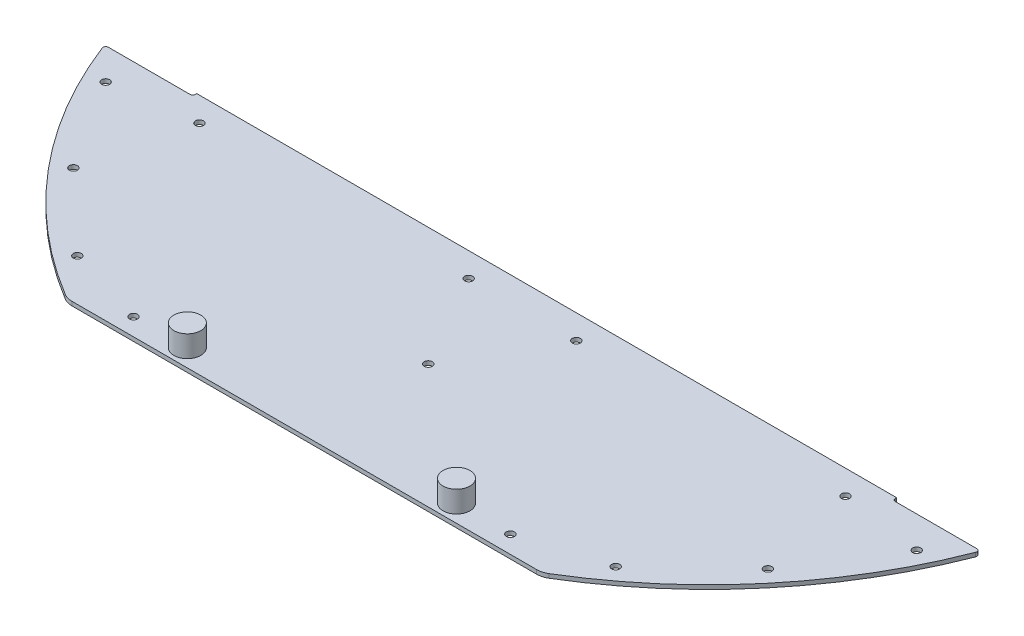
SolidWorks part; units mm, degrees
material "3.3535 (EN-AW 5754)"
ref_plane "Plan de face" through (0, 0, 0) normal (0, 0, 1) x (1, 0, 0)
ref_plane "Plan de dessus" through (0, 0, 0) normal (0, 1, 0) x (1, 0, 0)
ref_plane "Plan de droite" through (0, 0, 0) normal (1, 0, 0) x (0, 0, -1)
sketch "Esquisse1" plane through (0, 0, 0) normal (0, 1, 0) x (1, 0, 0)
  line L0 (0, 0) -> (0, -150) construction
  line L1 (-130, -60) -> (130, -60)
  line L2 (130, -60) -> (130, -61.5)
  line L3 (-88.1816, -150) -> (88.1816, -150)
  line L6 (162.769, -61.5) -> (130, -61.5)
  line L8 (-162.769, -61.5) -> (-130, -61.5)
  line L9 (-130, -60) -> (-130, -61.5)
  circle A0 centre (-120, -69) radius 1.5
  circle A1 centre (-20, -69) radius 1.5
  circle A2 centre (20, -69) radius 1.5
  circle A3 centre (120, -69) radius 1.5
  circle A4 centre (0, -104) radius 1.5
  arc A10 (-162.769, -61.5) -> (-88.1816, -150) centre (0, 0) ccw
  arc A11 (88.1816, -150) -> (162.769, -61.5) centre (0, 0) ccw
  dimension "D2" = 60
  dimension "D3" = 9
  dimension "D4" = 3
  dimension "D5" = 240
  dimension "D7" = 40
  dimension "D8" = 44
  dimension "D10" = 260
  dimension "D12" = 1.5
  dimension "D13" = 348
  dimension "D6" = 150
extrude "Boss.-Extru.1" add sketch "Esquisse1" along normal blind 1.5
fillet "Congé1" radius 7 2 edges at (88.1816, 0.75, 150) (-88.1816, 0.75, 150)
fillet "Congé2" radius 1 4 edges at (-130, 0.75, 61.5) (130, 0.75, 61.5) (162.769, 0.75, 61.5) (-162.769, 0.75, 61.5)
sketch "Esquisse2" plane through (0, 1.5, 0) normal (0, 1, 0) x (1, 0, 0)
  line L0 (-150.6593, -73.1985) -> (-129.0082, -106.8322) construction
  line L1 (-129.0082, -106.8322) -> (-100, -134.3735) construction
  line L2 (0, 0) -> (0, -150) construction
  line L3 (-86.2554, -150) -> (86.2554, -150) construction
  circle A0 centre (-150.6593, -73.1985) radius 1.5
  circle A1 centre (-129.0082, -106.8322) radius 1.5
  circle A2 centre (-100, -134.3735) radius 1.5
  circle A3 centre (-70, -143.5) radius 1.5
  circle A4 centre (-50, -143.5) radius 1.5
  circle A5 centre (0, 0) radius 167.5 construction
  circle A6 centre (150.6593, -73.1985) radius 1.5
  circle A7 centre (129.0082, -106.8322) radius 1.5
  circle A8 centre (100, -134.3735) radius 1.5
  circle A9 centre (70, -143.5) radius 1.5
  circle A10 centre (50, -143.5) radius 1.5
  arc A11 (-162.2481, -62.8613) -> (-89.8709, -148.994) centre (0, 0) ccw construction
  dimension "D1" = 40
  dimension "D2" = 3
  dimension "D4" = 6.5
  dimension "D5" = 140
  dimension "D6" = 100
  dimension "D7" = 6.5
  dimension "D3" = 100
extrude "Enlèv. mat.-Extru.1" cut sketch "Esquisse2" against normal through all
sketch "Esquisse3" plane through (0, 1.5, 0) normal (0, 1, 0) x (1, 0, 0)
  circle A0 centre (-50, -143.5) radius 5
  circle A1 centre (50, -143.5) radius 5
  circle A2 centre (-50, -143.5) radius 1.5 construction
  circle A3 centre (50, -143.5) radius 1.5 construction
  dimension "D1" = 10
extrude "Boss.-Extru.2" add sketch "Esquisse3" along normal blind 8 separate body
